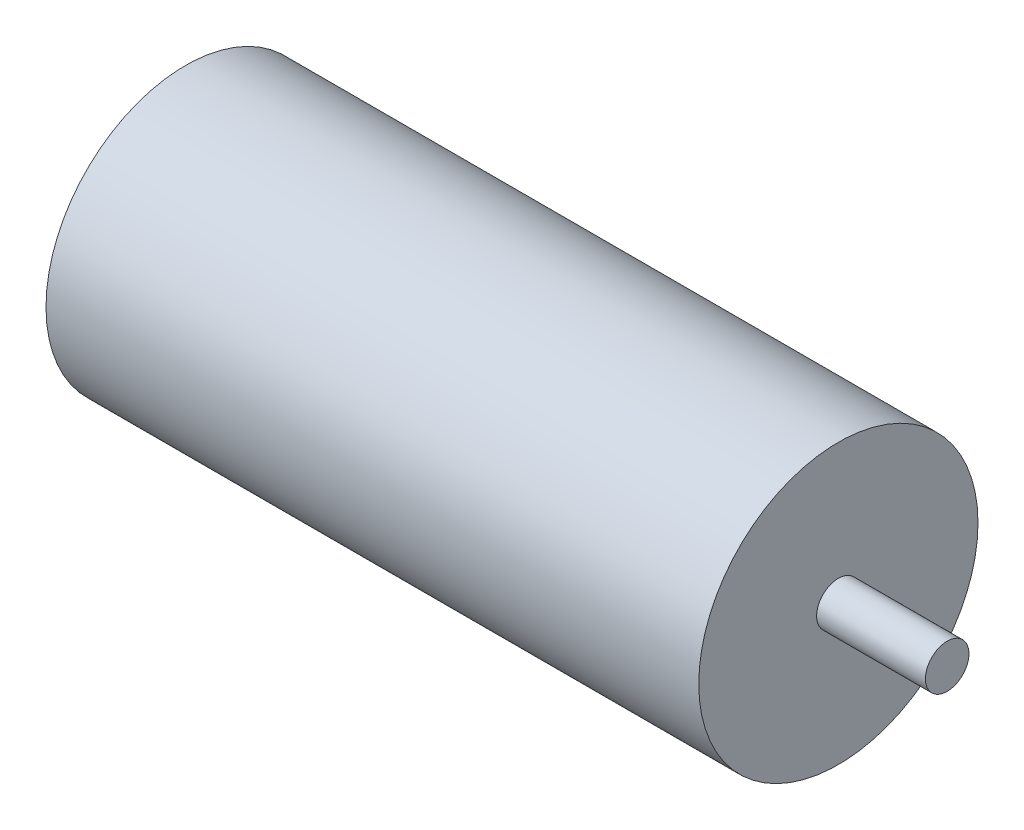
SolidWorks part; units mm, degrees
ref_plane "Front Plane" through (0, 0, 0) normal (0, 0, 1) x (1, 0, 0)
ref_plane "Top Plane" through (0, 0, 0) normal (0, 1, 0) x (1, 0, 0)
ref_plane "Right Plane" through (0, 0, 0) normal (1, 0, 0) x (0, 0, -1)
sketch "Sketch1" plane through (0, 0, 0) normal (1, 0, 0) x (0, 0, -1)
  circle A0 centre (0, 0) radius 6
  circle A1 centre (0, 0) radius 38.5
  dimension "D1" = 77
  dimension "D2" = 12
extrude "Boss-Extrude1" add sketch "Sketch1" along normal blind 180 contours A1 A0 region at (0, 0, 37.4111)
extrude "Boss-Extrude2" add sketch "Sketch1<3>" along normal blind 210 and the other way blind 15 contours A0 region at (0, 0, 0)
sketch "Sketch1<3>" plane through (0, 0, 0) normal (1, 0, 0) x (0, 0, -1) same geometry as "Sketch1"
